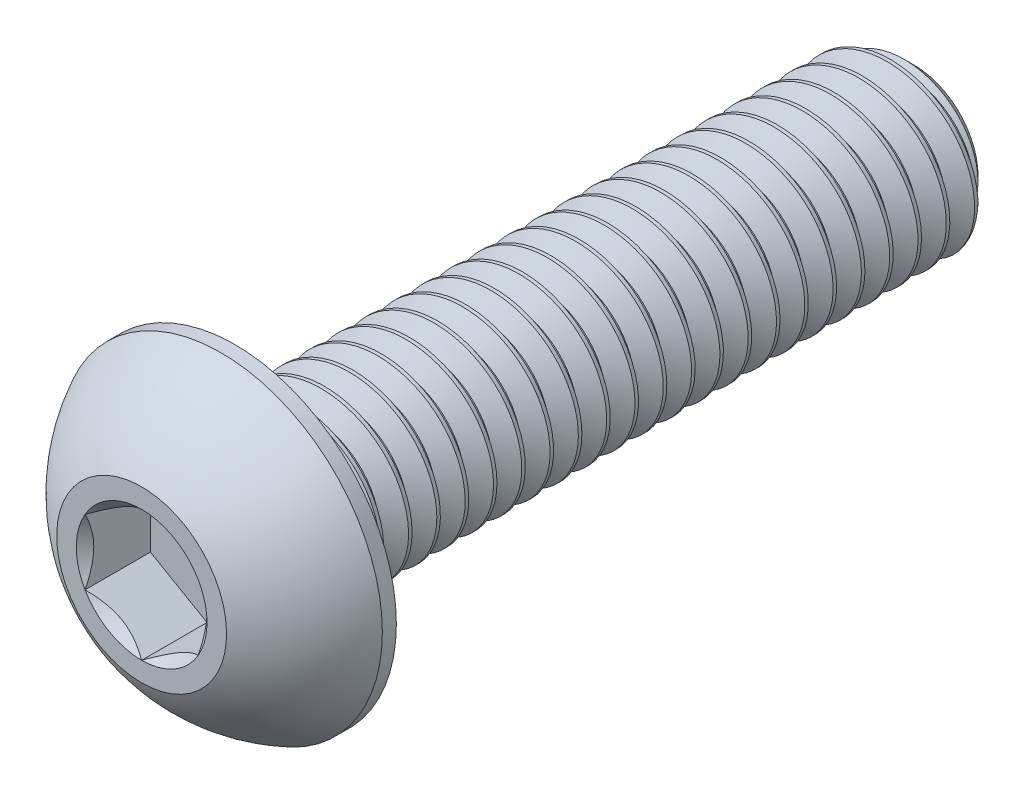
SolidWorks part; units mm, degrees
ref_plane "Front" through (0, 0, 0) normal (0, 0, 1) x (1, 0, 0)
ref_plane "Top" through (0, 0, 0) normal (0, 1, 0) x (1, 0, 0)
ref_plane "Right" through (0, 0, 0) normal (1, 0, 0) x (0, 0, -1)
sketch "Sketch1" plane through (0, 0, 0) normal (1, 0, 0) x (0, 0, -1)
  line L2 (1.65, 1.5) -> (13.65, 1.5)
  line L3 (13.65, 1.5) -> (13.65, 0)
  line L4 (13.65, 0) -> (1.65, 0)
  line L6 (1.4025, 2.85) -> (1.65, 2.85) construction
  line L7 (13.65, 1.5) -> (13.65, -1.5) construction
  line L8 (0, 0) -> (1.65, 0) construction
  line L9 (1.65, 2.85) -> (1.65, -2.85) construction
  line L11 (1.65, 1.5) -> (1.65, 0)
  line L13 (0, 1) -> (0, -1) construction
  line L14 (0, 1) -> (0, 1.5) construction
  arc A3 (0, 1.5) -> (1.4025, 2.85) centre (2.7948, 0) cw construction
  dimension "D1" = 0.2475
revolve "Revolve1" add sketch "Sketch1" angle 360 mid plane about L4
sketch "Sketch3" plane through (0, 0, -13.65) normal (0, 0, -1) x (-1, 0, 0)
  circle A0 centre (0, 0) radius 1.5
curve "Helix/Spiral1" pitch 0.5 height 12.5 radius 1.5 centre (0, 0, -13.65) axis (0, 0, 1) start towards (0, 1, 0)
sketch "Sketch2" plane through (0, 0, 0) normal (1, 0, 0) x (0, 0, -1)
  line L0 (13.65, 1.5) -> (14.0875, 1.5)
  line L1 (14.0875, 1.5) -> (13.9, 1.1752)
  line L2 (13.9, 1.1752) -> (13.8375, 1.1752)
  line L3 (13.8375, 1.1752) -> (13.65, 1.5)
  line L4 (13.7438, 1.3376) -> (13.9938, 1.3376) construction
  dimension "D1" = 60
  dimension "D2" = 0.0625
  dimension "D3" = 0.25
chamfer "Chamfer1" distance 0.375 angle 45 1 edges at (0, 1.5, -13.65)
sweep "Cut-Sweep1" cut profiles "Sketch2" path "Helix/Spiral1"
sketch "Sketch7" plane through (0, 0, 0) normal (1, 0, 0) x (0, 0, -1)
  line L6 (1.4025, 2.85) -> (1.65, 2.85) construction
  line L8 (0, 0) -> (1.65, 0) construction
  line L11 (1.65, 2.85) -> (1.65, -2.85) construction
  line L12 (1.4025, 2.85) -> (1.65, 2.85)
  line L13 (0, 0) -> (1.65, 0)
  line L14 (0, 1) -> (0, -1) construction
  line L15 (1.65, 2.85) -> (1.65, 0)
  line L16 (0, 1.5) -> (0, 0)
  arc A2 (1.4025, 2.85) -> (0, 1.5) centre (2.7948, 0) ccw construction
  arc A3 (1.4025, 2.85) -> (0, 1.5) centre (2.7948, 0) ccw
revolve "Revolve2" add sketch "Sketch7" angle 360 mid plane about L13
sketch "Sketch5" plane through (0, 0, 0) normal (0, 0, 1) x (1, 0, 0)
  line L1 (1, -0.5774) -> (1, 0.5774)
  line L2 (1, 0.5774) -> (0, 1.1547)
  line L3 (0, 1.1547) -> (-1, 0.5774)
  line L4 (-1, 0.5774) -> (-1, -0.5774)
  line L5 (-1, -0.5774) -> (0, -1.1547)
  line L6 (0, -1.1547) -> (1, -0.5774)
  circle A0 centre (0, 0) radius 1 construction
extrude "Cut-Extrude2" cut sketch "Sketch5" against normal blind 1.155
sketch "Sketch6" plane through (0, 0, 0) normal (0, 0, 1) x (1, 0, 0)
  circle A0 centre (0, 0) radius 1.1547
extrude "Cut-Extrude3" cut sketch "Sketch6" against normal blind 1.155 draft 45
sketch "Sketch9" [suppressed] plane through (0, 0, -4.2164) normal (0, 0, 1) x (1, 0, 0)
  circle A2 centre (0, 0) radius 3.9687
extrude "Boss-Extrude2" [suppressed] add sketch "Sketch9" against normal offset from surface (9.525 mm away) 28.575 up to face at (0, 1.125, -13.65)
sketch "Sketch10" plane through (0, 0, 0) normal (1, 0, 0) x (0, 0, -1)
  line L0 (13.65, 1.5) -> (13.65, -1.5) construction
  point P0 (12.9, -1.5)
  dimension "D1" = 0.75
equation "\"D3@Helix/Spiral1\" = \"Lg@Sketch1\" + \"D4@Helix/Spiral1\""
equation "\"D2@Sketch2\" = \"D4@Helix/Spiral1\" * .125"
equation "\"D3@Sketch2\" = \"D4@Helix/Spiral1\" * .5"
equation "\"D1@Chamfer1\" = \"D4@Helix/Spiral1\" * .75"
equation "\"D1@Cut-Extrude2\" = \"Head Ht@Sketch1\" * .7"
equation "\"D1@Sketch1\" = \"Head Ht@Sketch1\" * .15"
equation "\"D1@Sketch10\" = \"D4@Helix/Spiral1\" * 1.5"
equation "\"D1@Cut-Extrude3\" = \"D1@Cut-Extrude2\""
